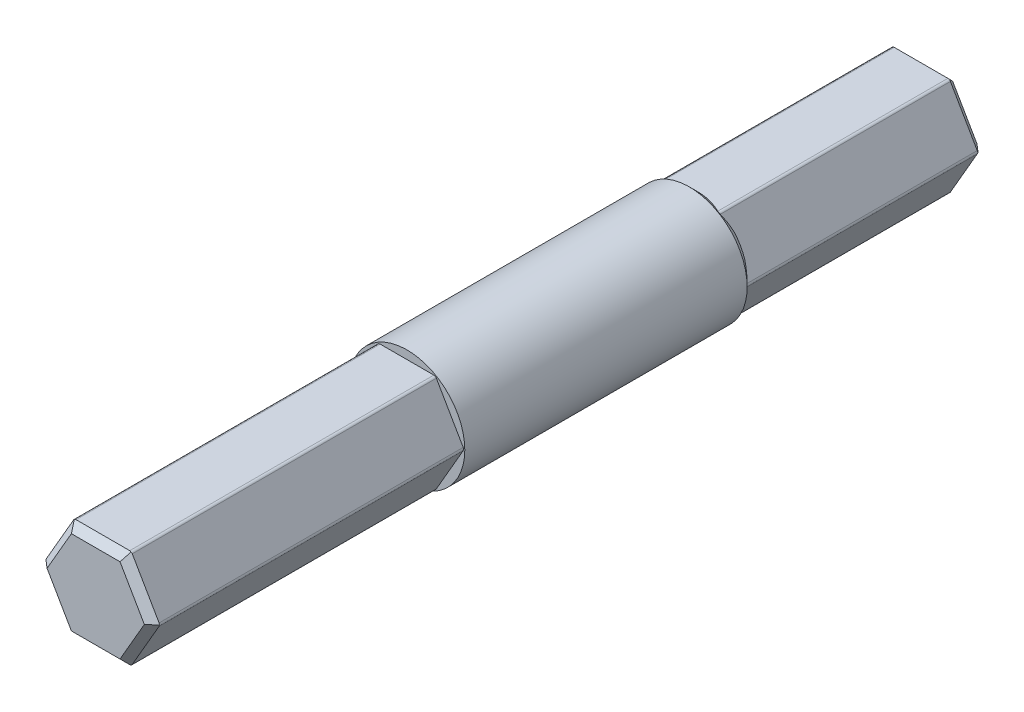
SolidWorks part; units mm, degrees
material "PETG"
ref_plane "Front Plane" through (0, 0, 0) normal (0, 0, 1) x (1, 0, 0)
ref_plane "Top Plane" through (0, 0, 0) normal (0, 1, 0) x (1, 0, 0)
ref_plane "Right Plane" through (0, 0, 0) normal (1, 0, 0) x (0, 0, -1)
sketch "Sketch1" plane through (0, 0, 0) normal (0, 0, 1) x (1, 0, 0)
  circle A0 centre (0, 0) radius 3.99
  dimension "Shaft Dia" = 7.98
extrude "Boss-Extrude1" add sketch "Sketch1" along normal blind 20
sketch "Sketch2" plane through (0, 0, 20) normal (0, 0, 1) x (1, 0, 0)
  line L1 (4, 0) -> (2, 3.4641) construction
  line L2 (2, 3.4641) -> (-2, 3.4641) construction
  line L3 (-2, 3.4641) -> (-4, 0) construction
  line L4 (-4, 0) -> (-2, -3.4641) construction
  line L5 (-2, -3.4641) -> (2, -3.4641) construction
  line L6 (2, -3.4641) -> (4, 0) construction
  line L7 (3.9365, 0) -> (1.9682, 3.4091)
  line L8 (1.9682, 3.4091) -> (-1.9682, 3.4091)
  line L9 (-1.9682, 3.4091) -> (-3.9365, 0)
  line L10 (-3.9365, 0) -> (-1.9682, -3.4091)
  line L11 (-1.9682, -3.4091) -> (1.9682, -3.4091)
  line L12 (1.9682, -3.4091) -> (3.9365, 0)
  circle A0 centre (0, 0) radius 3.4641 construction
  circle A1 centre (0, 0) radius 3.4091 construction
  dimension "Hex Circumscribed Nominal Dia" = 8
  dimension "Hex Flat To Flat Offset" = 0.055
extrude "Boss-Extrude2" add sketch "Sketch2" along normal blind 21.5
sketch "Sketch3" plane through (0, 0, 0) normal (0, 0, -1) x (-1, 0, 0)
  line L0 (-1.9682, 3.4091) -> (1.9682, 3.4091) construction
  line L13 (3.9365, 0) -> (1.9682, 3.4091)
  line L14 (1.9682, 3.4091) -> (-1.9682, 3.4091)
  line L15 (-1.9682, 3.4091) -> (-3.9365, 0)
  line L16 (-3.9365, 0) -> (-1.9682, -3.4091)
  line L17 (-1.9682, -3.4091) -> (1.9682, -3.4091)
  line L18 (1.9682, -3.4091) -> (3.9365, 0)
  circle A1 centre (0, 0) radius 3.4091 construction
extrude "Boss-Extrude3" add sketch "Sketch3" along normal blind 16
chamfer "Chamfer1" distance 0.5 angle 45 12 edges at (0, -3.4091, 41.5) (-2.9524, -1.7046, 41.5) (-2.9524, 1.7046, 41.5) (0, 3.4091, 41.5) (2.9524, 1.7046, 41.5) (2.9524, -1.7046, 41.5) (0, -3.4091, -16) (2.9524, -1.7046, -16) (2.9524, 1.7046, -16) (0, 3.4091, -16) (-2.9524, 1.7046, -16) (-2.9524, -1.7046, -16)
fillet "Fillet1" radius 0.2 12 edges at (-1.9682, 3.4091, -7.75) (-3.9365, 0, -7.75) (1.9682, 3.4091, -7.75) (3.9365, 0, -7.75) (1.9682, -3.4091, -7.75) (-1.9682, -3.4091, -7.75) (1.9682, -3.4091, 30.5) (-1.9682, -3.4091, 30.5) (-3.9365, 0, 30.5) (-1.9682, 3.4091, 30.5) (3.9365, 0, 30.5) (1.9682, 3.4091, 30.5)
chamfer "Chamfer2" distance 0.5 angle 45 1 edges at (3.99, 0, 0)
equation "\"tol_dia_id_intfc\" = 0.0200mm ' For hole diameters - Interference fit"
equation "\"tol_dia_id_slip\"  = 0.0300mm ' For hole diameters - Slip fit"
equation "\"tol_dia_id_clear\" = 0.0500mm ' For hole diameters - Clearance fit"
equation "\"tol_dia_od_intfc\" = 0.0200mm ' For shaft diameters - Interference fit"
equation "\"tol_dia_od_slip\"  = 0.0300mm ' For shaft diameters - Slip fit"
equation "\"tol_dia_od_clear\" = 0.0500mm ' For shaft diameters - Clearance fit"
equation "\"tol_general_intfc\"= 0.0030mm ' For general parts (Horiz) - Interference fit"
equation "\"tol_general_slip\" = 0.0050mm ' For general parts (Horiz) - Slip fit"
equation "\"tol_general_clear\"= 0.0100mm ' For general parts (Horiz) - Clearance fit"
equation "\"tol_layer_intfc\"  = 0.0030mm ' For all parts (Vert) - Interference fit"
equation "\"tol_layer_slip\"   = 0.0050mm ' For all parts (Vert) - Slip fit"
equation "\"tol_layer_clear\"  = 0.0100mm ' For all parts (Vert) - Clearance fit"
equation "\"tol_corner_rad\"   = 0.100mm ' For corners that fit into other parts"
equation "\"Shaft Dia@Sketch1\" = \"nominal_dia\" - \"tol_dia_od_intfc\""
equation "\"nominal_dia\"= 8.00mm"
equation "\"Hex Circumscribed Nominal Dia@Sketch2\" = \"nominal_dia\""
equation "\"Hex Flat To Flat Offset@Sketch2\"=\"tol_general_slip\"+0.050"
equation "\"D1@Fillet1\"=\"tol_corner_rad\"*2"
equation "\"D1@Boss-Extrude2\"=21.5"
